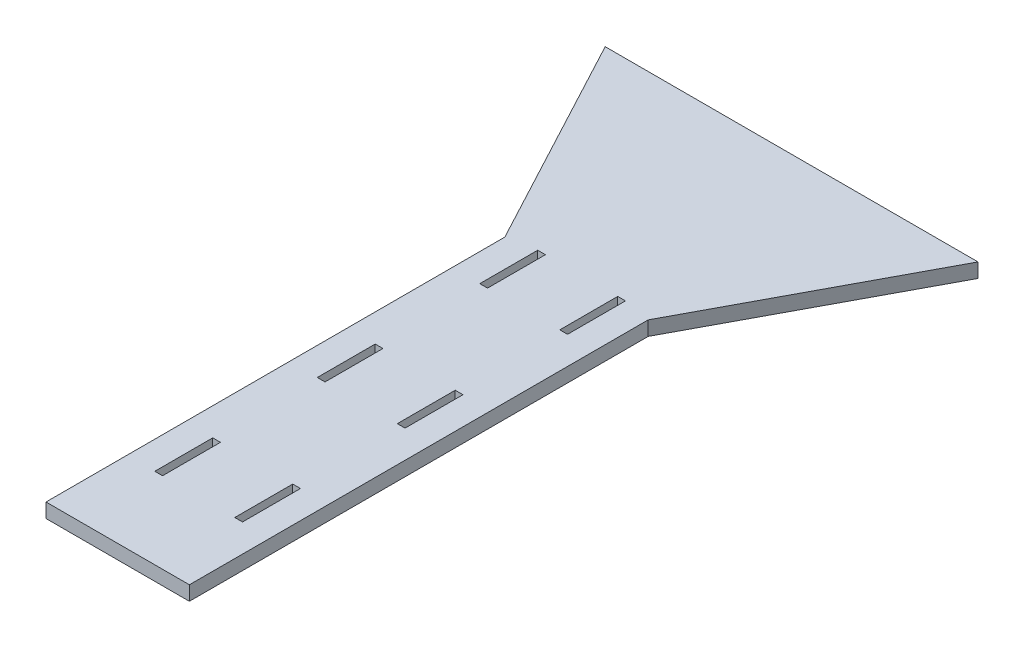
SolidWorks part; units mm, degrees
material "PC High Viscosity"
ref_plane "Front" through (0, 0, 0) normal (0, 0, 1) x (1, 0, 0)
ref_plane "Top" through (0, 0, 0) normal (0, 1, 0) x (1, 0, 0)
ref_plane "Right" through (0, 0, 0) normal (1, 0, 0) x (0, 0, -1)
sketch "Sketch1" plane through (0, 0, 0) normal (0, 1, 0) x (1, 0, 0)
  line L0 (-31.75, 0) -> (31.75, 0)
  line L1 (31.75, 0) -> (31.75, 203.2)
  line L2 (31.75, 203.2) -> (82.55, 298.45)
  line L3 (82.55, 298.45) -> (-82.55, 298.45)
  line L4 (-82.55, 298.45) -> (-31.75, 203.2)
  line L5 (-31.75, 203.2) -> (-31.75, 0)
  point P4 (0, 0)
  dimension "D1" = 63.5
  dimension "D2" = 203.2
  dimension "D3" = 95.25
  dimension "D4" = 165.1
extrude "Boss-Extrude1" add sketch "Sketch1" along normal blind 6.35
sketch "Sketch2" plane through (0, 6.35, 0) normal (0, 1, 0) x (1, 0, 0)
  line L4 (-19.431, 61.5103) -> (-19.431, 35.8563)
  line L5 (-19.431, 35.8563) -> (-16.002, 35.8563)
  line L6 (-16.002, 35.8563) -> (-16.002, 61.5103)
  line L7 (-16.002, 61.5103) -> (-19.431, 61.5103)
  line L8 (-19.431, 61.5103) -> (-19.431, 35.8563)
  line L9 (-19.431, 35.8563) -> (-16.002, 35.8563)
  line L10 (-16.002, 35.8563) -> (-16.002, 61.5103)
  line L11 (-16.002, 61.5103) -> (-19.431, 61.5103)
  line L12 (-19.431, 133.477) -> (-19.431, 107.823)
  line L13 (-19.431, 107.823) -> (-16.002, 107.823)
  line L14 (-16.002, 107.823) -> (-16.002, 133.477)
  line L15 (-16.002, 133.477) -> (-19.431, 133.477)
  line L16 (-19.431, 133.477) -> (-19.431, 107.823)
  line L17 (-19.431, 107.823) -> (-16.002, 107.823)
  line L18 (-16.002, 107.823) -> (-16.002, 133.477)
  line L19 (-16.002, 133.477) -> (-19.431, 133.477)
  line L24 (-19.431, 205.4437) -> (-19.431, 179.7897)
  line L25 (-19.431, 179.7897) -> (-16.002, 179.7897)
  line L26 (-16.002, 179.7897) -> (-16.002, 205.4437)
  line L27 (-16.002, 205.4437) -> (-19.431, 205.4437)
  line L28 (-19.431, 205.4437) -> (-19.431, 179.7897)
  line L29 (-19.431, 179.7897) -> (-16.002, 179.7897)
  line L30 (-16.002, 179.7897) -> (-16.002, 205.4437)
  line L31 (-16.002, 205.4437) -> (-19.431, 205.4437)
  line L36 (16.002, 205.4437) -> (16.002, 179.7897)
  line L37 (16.002, 179.7897) -> (19.431, 179.7897)
  line L38 (19.431, 179.7897) -> (19.431, 205.4437)
  line L39 (19.431, 205.4437) -> (16.002, 205.4437)
  line L40 (16.002, 205.4437) -> (16.002, 179.7897)
  line L41 (16.002, 179.7897) -> (19.431, 179.7897)
  line L42 (19.431, 179.7897) -> (19.431, 205.4437)
  line L43 (19.431, 205.4437) -> (16.002, 205.4437)
  line L48 (16.002, 133.477) -> (16.002, 107.823)
  line L49 (16.002, 107.823) -> (19.431, 107.823)
  line L50 (19.431, 107.823) -> (19.431, 133.477)
  line L51 (19.431, 133.477) -> (16.002, 133.477)
  line L52 (16.002, 133.477) -> (16.002, 107.823)
  line L53 (16.002, 107.823) -> (19.431, 107.823)
  line L54 (19.431, 107.823) -> (19.431, 133.477)
  line L55 (19.431, 133.477) -> (16.002, 133.477)
  line L60 (16.002, 61.5103) -> (16.002, 35.8563)
  line L61 (16.002, 35.8563) -> (19.431, 35.8563)
  line L62 (19.431, 35.8563) -> (19.431, 61.5103)
  line L63 (19.431, 61.5103) -> (16.002, 61.5103)
  line L64 (16.002, 61.5103) -> (16.002, 35.8563)
  line L65 (16.002, 35.8563) -> (19.431, 35.8563)
  line L66 (19.431, 35.8563) -> (19.431, 61.5103)
  line L67 (19.431, 61.5103) -> (16.002, 61.5103)
  dimension "D1" = 0.127
  dimension "D2" = 0.127
  dimension "D3" = 0.127
  dimension "D4" = 0.127
  dimension "D5" = 0.127
  dimension "D6" = 0.127
extrude "Cut-Extrude1" cut sketch "Sketch2" against normal through all
